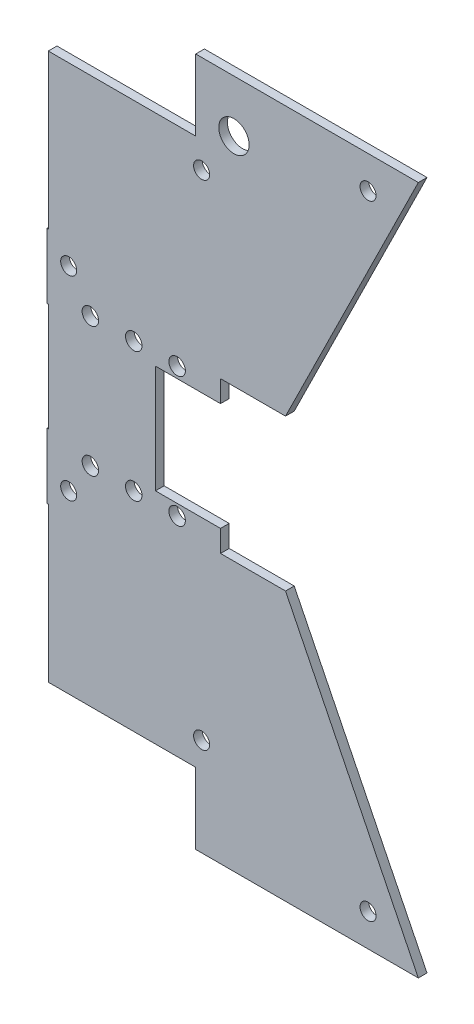
SolidWorks part; units mm, degrees
material "Thornel Mat VMA"
ref_plane "Front Plane" through (0, 0, 0) normal (0, 0, 1) x (1, 0, 0)
ref_plane "Top Plane" through (0, 0, 0) normal (0, 1, 0) x (1, 0, 0)
ref_plane "Right Plane" through (0, 0, 0) normal (1, 0, 0) x (0, 0, -1)
sketch "Sketch1" plane through (0, 0, 0) normal (0, 0, 1) x (1, 0, 0)
  line L0 (-2.9301, -104.5098) -> (-3.3149, -104.5098)
  line L1 (-3.3149, -72.8868) -> (-2.9301, -72.8868)
  line L78 (47.4851, -66.5368) -> (47.4851, -72.8868)
  line L79 (47.4851, -104.5098) -> (47.4851, -110.8598)
  line L80 (66.5174, -66.5368) -> (105.3971, 12.1397)
  line L81 (105.3971, 12.1397) -> (38.7094, 12.1397)
  line L88 (38.7094, 12.1397) -> (38.7094, -8.6883)
  line L89 (-2.9301, -8.6883) -> (38.7094, -8.6883)
  line L90 (-3.3149, -53.8368) -> (-2.9301, -53.8368)
  line L91 (-2.9301, -53.8368) -> (-2.9301, -8.6883)
  line L92 (-3.3149, -66.5368) -> (-3.3149, -53.8368)
  line L93 (-3.3149, -72.8868) -> (-3.3149, -66.5368)
  line L94 (-2.9301, -104.5098) -> (-2.9301, -72.8868)
  line L95 (-3.3149, -110.8598) -> (-3.3149, -104.5098)
  line L96 (66.5174, -110.8598) -> (105.3971, -189.5363)
  line L97 (105.3971, -189.5363) -> (38.7094, -189.5363)
  line L98 (38.7094, -189.5363) -> (38.7094, -168.7083)
  line L99 (-2.9301, -168.7083) -> (38.7094, -168.7083)
  line L106 (-3.3149, -110.8598) -> (-3.3149, -123.5598)
  line L107 (-3.3149, -123.5598) -> (-2.9301, -123.5598)
  line L108 (66.5174, -110.8598) -> (47.4851, -110.8598)
  line L109 (47.4851, -66.5368) -> (66.5174, -66.5368)
  line L110 (47.4851, -104.5098) -> (47.4851, -72.8868)
  line L111 (-2.9301, -123.5598) -> (-2.9301, -168.7083)
  circle A0 centre (90.6739, 2.6147) radius 2.3495
  circle A1 centre (41.9566, -16.4353) radius 2.3495
  circle A2 centre (3.0351, -60.1868) radius 2.3495
  circle A3 centre (3.0351, -117.2098) radius 2.3495
  circle A4 centre (41.9566, -160.9613) radius 2.3495
  circle A5 centre (90.6739, -180.0113) radius 2.3495
  circle A6 centre (51.4094, -3.1003) radius 4.445
  point P2 (90.6739, 2.6147)
  point P4 (41.9566, -16.4353)
  point P6 (3.0351, -60.1868)
  point P8 (3.0351, -117.2098)
  point P10 (41.9566, -160.9613)
  point P11 (90.6739, -180.0113)
  dimension "D2" = 4.699
  dimension "D5" = 8.89
  dimension "D1" = 66.6876
  dimension "D3" = 12.7
  dimension "D4" = 15.24
extrude "Boss-Extrude1" add sketch "Sketch1" along normal blind 2.54
sketch "Sketch2" plane through (0, 0, 2.54) normal (0, 0, 1) x (1, 0, 0)
  line L0 (-3.3149, -53.8368) -> (-3.3149, -72.8868) construction
  line L1 (47.4851, -66.5368) -> (66.5174, -66.5368) construction
  line L2 (47.4851, -88.6983) -> (-2.9301, -88.6983) construction
  line L3 (47.4851, -110.8598) -> (47.4851, -66.5368) construction
  line L4 (-2.9301, -72.8868) -> (-2.9301, -104.5098) construction
  circle A0 centre (9.3851, -69.7118) radius 2.413
  circle A1 centre (22.0851, -69.7118) radius 2.413
  circle A2 centre (34.7851, -69.7118) radius 2.413
  circle A4 centre (34.7851, -107.6848) radius 2.413
  circle A5 centre (22.0851, -107.6848) radius 2.413
  circle A6 centre (9.3851, -107.6848) radius 2.413
  dimension "D1" = 4.826
  dimension "D2" = 4.826
  dimension "D3" = 4.826
  dimension "D4" = 12.7
  dimension "D5" = 12.7
  dimension "D6" = 12.7
  dimension "D7" = 3.175
  dimension "D8" = 0
  dimension "D9" = 0
extrude "Cut-Extrude1" cut sketch "Sketch2" against normal through all
sketch "Sketch3" plane through (0, 0, 2.54) normal (0, 0, 1) x (1, 0, 0)
  line L0 (47.4851, -110.8598) -> (47.4851, -66.5368) construction
  line L1 (47.4851, -72.8868) -> (28.4351, -72.8868)
  line L2 (47.4851, -72.8868) -> (47.4851, -104.5098)
  line L3 (47.4851, -104.5098) -> (28.4351, -104.5098)
  line L4 (28.4351, -72.8868) -> (28.4351, -104.5098)
  line L5 (47.4851, -66.5368) -> (66.5174, -66.5368) construction
  line L6 (66.5174, -110.8598) -> (47.4851, -110.8598) construction
  circle A0 centre (22.0851, -69.7118) radius 2.413 construction
  dimension "D3" = 6.35
  dimension "D1" = 6.35
  dimension "D2" = 6.35
extrude "Cut-Extrude2" cut sketch "Sketch3" against normal through all
sketch "Sketch4" plane through (0, 0, 2.54) normal (0, 0, 1) x (1, 0, 0)
  line L0 (-2.9301, -168.7083) -> (38.7094, -168.7083) construction
  line L1 (27.4577, 15.7469) -> (40.2334, 15.7469)
  line L2 (27.4577, 15.7469) -> (27.4577, -8.6883)
  line L3 (27.4577, -8.6883) -> (40.2334, -8.6883)
  line L4 (40.2334, 15.7469) -> (40.2334, -8.6883)
  line L5 (0, -197.042) -> (40.2334, -197.042)
  line L6 (0, -197.042) -> (0, -168.7083)
  line L7 (0, -168.7083) -> (40.2334, -168.7083)
  line L8 (40.2334, -197.042) -> (40.2334, -168.7083)
  line L9 (38.7094, -168.7083) -> (38.7094, -189.5363) construction
  line L10 (38.7094, -8.6883) -> (-2.9301, -8.6883) construction
  point P10 (40.8959, -197.042)
  dimension "D1" = 1.524
extrude "Cut-Extrude3" cut sketch "Sketch4" against normal through all
